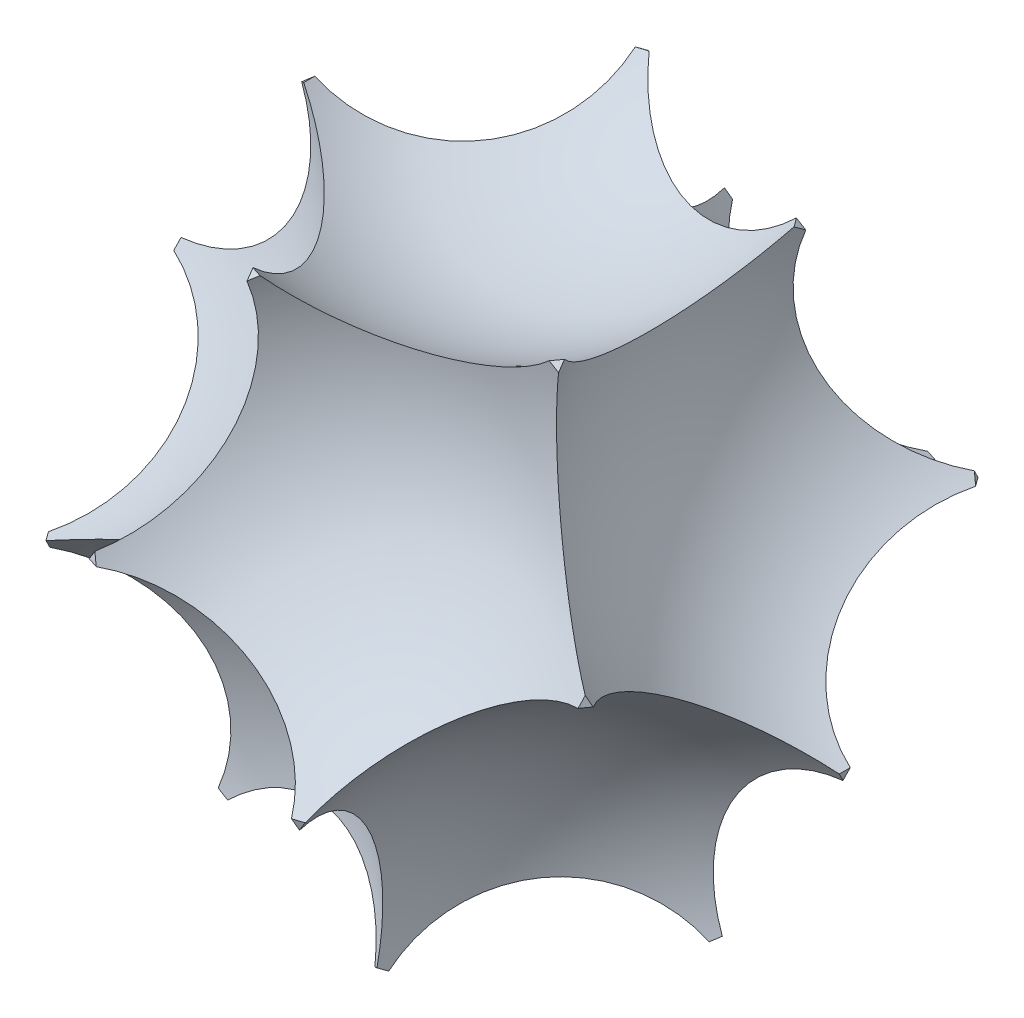
SolidWorks part; units mm, degrees
ref_plane "Front Plane" through (0, 0, 0) normal (0, 0, 1) x (1, 0, 0)
ref_plane "Top Plane" through (0, 0, 0) normal (0, 1, 0) x (1, 0, 0)
ref_plane "Right Plane" through (0, 0, 0) normal (1, 0, 0) x (0, 0, -1)
sketch "Sketch1" plane through (0, 0, 0) normal (0, 1, 0) x (1, 0, 0)
  line L0 (0, -62.5) -> (0, 62.5)
  arc A0 (0, 62.5) -> (0, -62.5) centre (0, 0) cw
  point P6 (0, 0)
  dimension "D1" = 125
revolve "Revolve1" add sketch "Sketch1" angle 360 about L0
sketch "Sketch2" plane through (0, 0, 0) normal (0, 0, 1) x (1, 0, 0)
  line L0 (0, 142.2647) -> (0, 34.7847)
  arc A0 (0, 142.2647) -> (0, 34.7847) centre (0, 88.5247) ccw
  dimension "D2" = 53.74
  dimension "D3" = 0
  dimension "D1" = 88.5247
revolve "Cut-Revolve1" cut sketch "Sketch2" angle 360 about L0
mirror "Mirror1" about plane through (0, 0, 0) normal (0, 1, 0) of "Cut-Revolve1"
ref_axis "Axis1" through (0, 0, -110) along (0, 0, 1)
ref_axis "Axis2" through (0, 73.6883, 0) along (0, -1, 0)
pattern_circular "CirPattern1" count 2 every 116.565 about axis through (0, 0, -110) along (0, 0, 1) of "Cut-Revolve1", "Mirror1"
pattern_circular "CirPattern2" count 5 every 72 about axis through (0, 73.6883, 0) along (0, -1, 0) of "CirPattern1"
